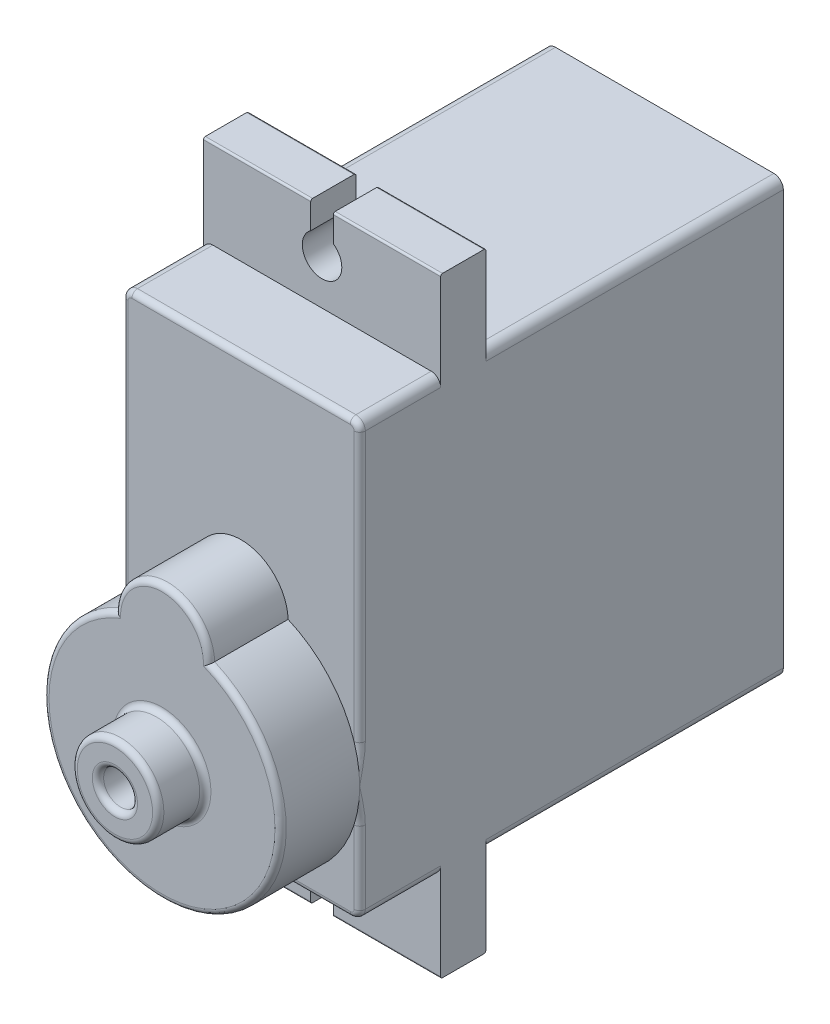
SolidWorks part; units mm, degrees
ref_plane "正面" through (0, 0, 0) normal (0, 0, 1) x (1, 0, 0)
ref_plane "平面" through (0, 0, 0) normal (0, 1, 0) x (1, 0, 0)
ref_plane "右側面" through (0, 0, 0) normal (1, 0, 0) x (0, 0, -1)
sketch "ｽｹｯﾁ1" plane through (0, 0, 0) normal (0, 0, 1) x (1, 0, 0)
  line L0 (-6.3, 11.5) -> (6.3, 11.5)
  line L1 (-6.3, -16.2) -> (6.3, -16.2)
  line L2 (-6.3, -16.2) -> (-6.3, 16.2)
  line L3 (-6.3, 16.2) -> (6.3, 16.2)
  line L4 (6.3, -16.2) -> (6.3, 16.2)
  line L5 (-6.3, -16.2) -> (6.3, 16.2) construction
  line L6 (-6.3, 16.2) -> (6.3, -16.2) construction
  line L7 (6.3, -11.5) -> (-6.3, -11.5)
  line L8 (0, -16.2) -> (0, 16.2) construction
  line L9 (-6.3, 13.9) -> (6.3, 13.9) construction
  line L10 (-0.6, 13.9) -> (-0.6, 16.2)
  line L11 (0.6, 13.9) -> (0.6, 16.2)
  line L12 (-6.3, 0) -> (6.3, 0) construction
  line L13 (-0.6, -13.9) -> (-0.6, -16.2)
  line L14 (0.6, -13.9) -> (0.6, -16.2)
  circle A0 centre (0, 13.9) radius 1.05
  circle A1 centre (0, -13.9) radius 1.05
  point P0 (0, 0)
  point P28 (-6.3, 0)
  point P29 (-6.3, 0)
  dimension "D3" = 2.1
  dimension "D1" = 0.6
  dimension "D2" = 0.6
  dimension "D4" = 13.9
  dimension "D5" = 32.4
  dimension "D6" = 11.5
  dimension "D7" = 11.5
  dimension "D8" = 12.6
extrude "ﾎﾞｽ - 押し出し1" add sketch "ｽｹｯﾁ1" along normal blind 22.5 contours L7 L4 L0 L2 region at (0, 0, 0)
extrude "ﾎﾞｽ - 押し出し2" add sketch "ｽｹｯﾁ1<4>" along normal blind 2.4 from offset 15.8 contours A0 L10 L3 L2 L0 L4 L11 | L13 A1 L14 L1 L4 L7 L2 region at (-6.1655, 13.85, 0) region at (0, -11.6345, 0)
sketch "ｽｹｯﾁ1<4>" plane through (0, 0, 0) normal (0, 0, 1) x (1, 0, 0) same geometry as "ｽｹｯﾁ1"
fillet "ﾌｨﾚｯﾄ1" radius 0.5 8 edges at (6.3, 11.5, 7.9) (6.3, 11.5, 20.35) (6.3, -11.5, 7.9) (6.3, -11.5, 20.35) (-6.3, 11.5, 7.9) (-6.3, 11.5, 20.35) (-6.3, -11.5, 7.9) (-6.3, -11.5, 20.35)
ref_plane "Layer_01" through (0, 0, 22.5) normal (0, 0, 1) x (1, 0, 0)
sketch "ｽｹｯﾁ2" plane through (0, 0, 22.5) normal (0, 0, 1) x (1, 0, 0)
  line L0 (-5.8, 11.5) -> (5.8, 11.5) construction
  line L1 (-6.3, -11.5) -> (6.3, -11.5) construction
  line L2 (-6.3, -11.5) -> (-6.3, 11.5) construction
  line L3 (-6.3, 11.5) -> (6.3, 11.5) construction
  line L4 (6.3, -11.5) -> (6.3, 11.5) construction
  line L5 (-6.3, -11.5) -> (6.3, 11.5) construction
  line L6 (-6.3, 11.5) -> (6.3, -11.5) construction
  line L7 (-6.3, -11) -> (-6.3, 11) construction
  line L8 (6.3, -11) -> (6.3, 11) construction
  line L9 (5.8, -11.5) -> (-5.8, -11.5) construction
  line L10 (0, 0) -> (0, -11.5) construction
  line L11 (0, -11.5) -> (0, 3) construction
  circle A0 centre (0, -5.2) radius 6.3
  circle A1 centre (0, -5.2) radius 2.3
  circle A2 centre (0, -5.2) radius 0.9
  circle A3 centre (0, 0.5) radius 2.5
  point P4 (0, 0)
  dimension "D1" = 6.3
  dimension "D2" = 4.6
  dimension "D3" = 1.8
  dimension "D5" = 5
  dimension "D4" = 14.5
extrude "ﾎﾞｽ - 押し出し4" add sketch "ｽｹｯﾁ2" along normal blind 4.2 contours A0 A3 | A0 A3 | A3 A0 A1 region at (-3.3645, -10.3187, 22.5) region at (0, -0.3266, 22.5) region at (0, 1.7909, 22.5)
extrude "ﾎﾞｽ - 押し出し5" add sketch "ｽｹｯﾁ2<4>" along normal blind 6.7 contours A1 A2 region at (-2.2349, -5.2, 22.5)
sketch "ｽｹｯﾁ2<4>" plane through (0, 0, 22.5) normal (0, 0, 1) x (1, 0, 0) same geometry as "ｽｹｯﾁ2"
fillet "ﾌｨﾚｯﾄ2" radius 0.1 8 edges at (-3.45, 16.2, 18.2) (-3.45, 16.2, 15.8) (3.45, 16.2, 15.8) (3.45, 16.2, 18.2) (-3.45, -16.2, 15.8) (3.45, -16.2, 15.8) (3.45, -16.2, 18.2) (-3.45, -16.2, 18.2)
fillet "ﾌｨﾚｯﾄ4" radius 0.3 1 edges at (2.3, -5.2, 29.2)
fillet "ﾌｨﾚｯﾄ5" radius 0.3 1 edges at (0.9, -5.2, 29.2)
fillet "ﾌｨﾚｯﾄ6" radius 0.3 11 edges at (6.3, 2.9, 22.5) (6.1536, 11.3536, 22.5) (6.1536, -11.3536, 22.5) (6.3, -8.1, 22.5) (2.9, -11.5, 22.5) (-2.9, -11.5, 22.5) (-6.1536, -11.3536, 22.5) (-6.3, -8.1, 22.5) (0, 11.5, 22.5) (-6.1536, 11.3536, 22.5) (-6.3, 2.9, 22.5)
fillet "ﾌｨﾚｯﾄ8" radius 0.3 3 edges at (2.3, -5.2, 26.7) (0, -11.5, 26.7) (0, 3, 26.7)
